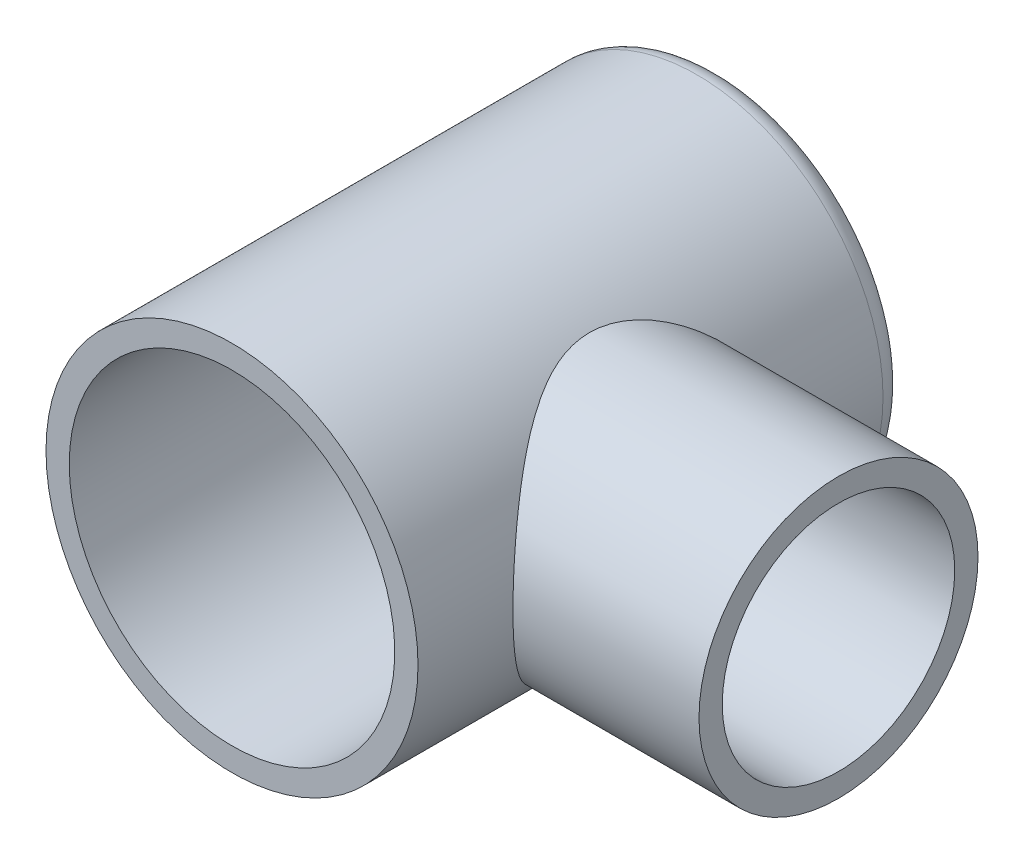
SolidWorks part; units mm, degrees
ref_plane "Front Plane" through (0, 0, 0) normal (0, 0, 1) x (1, 0, 0)
ref_plane "Top Plane" through (0, 0, 0) normal (0, 1, 0) x (1, 0, 0)
ref_plane "Right Plane" through (0, 0, 0) normal (1, 0, 0) x (0, 0, -1)
sketch "Sketch1" plane through (0, 0, 0) normal (0, 1, 0) x (1, 0, 0)
  line L0 (0, 0) -> (0, -8)
  line L1 (0, 0) -> (0, -3) construction
  line L2 (0, -3) -> (8, -3) construction
  dimension "D1" = 8
ref_plane "Plane3" through (0, 0, 8) normal (0, 0, 1) x (1, 0, 0)
sketch "Sketch2" plane through (0, 0, 8) normal (0, 0, 1) x (1, 0, 0)
  circle A0 centre (0, 0) radius 4
  circle A1 centre (0, 0) radius 3.5
extrude "Boss-Extrude1" add sketch "Sketch2" along normal blind 10
mirror "Mirror2" about plane through (0, 0, 8) normal (0, 0, 1) of bodies 101
delete or keep bodies "Body-Delete/Keep 2" type delete bodies bodies 101
ref_plane "Plane4" through (8, 0, 3) normal (1, 0, 0) x (0, 0, -1)
sketch "Sketch3" plane through (8, 0, 3) normal (1, 0, 0) x (0, 0, -1)
  line L0 (3, 0) -> (-5, 0) construction
  circle A0 centre (0.0426, 0) radius 3
  circle A1 centre (0.0426, 0) radius 2.5
extrude "Boss-Extrude2" add sketch "Sketch3" against normal up to surface (4 mm away) up to face at (4, 0, -2)
sketch "Sketch4" plane through (0, 0, -2) normal (0, 0, -1) x (-1, 0, 0)
  circle A0 centre (0, 0) radius 4
extrude "Boss-Extrude3" add sketch "Sketch4" along normal blind 0.5
fillet "Fillet2" radius 0.5 1 edges at (-4, 0, -2.5)
